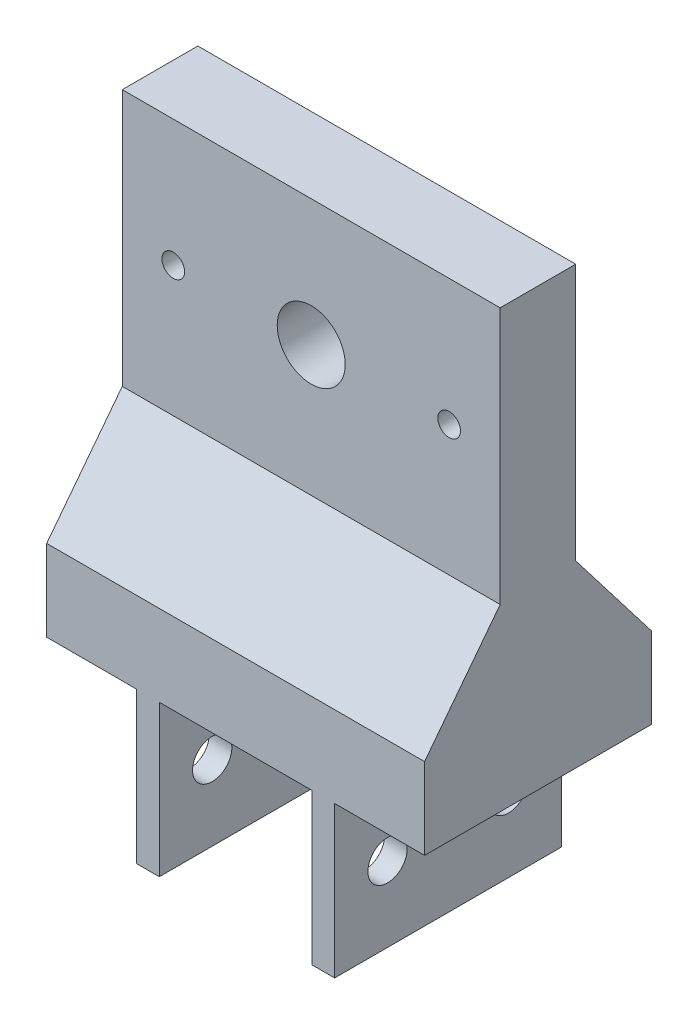
SolidWorks part; units mm, degrees
ref_plane "前视基准面" through (0, 0, 0) normal (0, 0, 1) x (1, 0, 0)
ref_plane "上视基准面" through (0, 0, 0) normal (0, 1, 0) x (1, 0, 0)
ref_plane "右视基准面" through (0, 0, 0) normal (1, 0, 0) x (0, 0, -1)
other "Configuration Table"
sketch "草图1" plane through (0, 0, 0) normal (0, 0, 1) x (1, 0, 0)
  line L0 (0, -39.6057) -> (0, 25.2485) construction
  line L9 (10.1, -25.375) -> (13.1, -25.375)
  line L10 (-25, -5.375) -> (-13.1, -5.375)
  line L11 (-25, -5.375) -> (-25, 5.375)
  line L12 (-25, 5.375) -> (25, 5.375)
  line L13 (25, -5.375) -> (25, 5.375)
  line L14 (-25, -5.375) -> (25, 5.375) construction
  line L15 (-25, 5.375) -> (25, -5.375) construction
  line L16 (-10.1, -5.375) -> (10.1, -5.375)
  line L17 (-13.1, -5.375) -> (-13.1, -25.375)
  line L18 (-13.1, -25.375) -> (-10.1, -25.375)
  line L19 (13.1, -5.375) -> (13.1, -25.375)
  line L21 (-10.1, -25.375) -> (-10.1, -5.375)
  line L22 (-10.1, -5.375) -> (10.1, -5.375)
  line L23 (10.1, -25.375) -> (10.1, -5.375)
  line L24 (-8.4435, -45.2703) -> (10.1, -5.375) construction
  line L25 (-10.1, -5.375) -> (10.5079, -49.7116) construction
  line L26 (-10.1, -5.375) -> (10.1, -5.375)
  line L27 (13.1, -5.375) -> (25, -5.375)
  point P2 (0, 0)
  point P12 (0, -27.1045)
  dimension "D1" = 50
  dimension "D2" = 10.75
  dimension "D3" = 20
  dimension "D4" = 3
  dimension "D5" = 20.2
extrude "凸台-拉伸1" add sketch "草图1" along normal blind 30 contours L19 L27 L13 L12 L11 L10 L17 L18 L21 L16 L23 L9 region at (0, -2.8061, 0)
sketch "草图2" plane through (0, 5.375, 0) normal (0, 1, 0) x (1, 0, 0)
  line L5 (-25, -30) -> (-25, 0) construction
  line L6 (-25, -10) -> (25, -10)
  line L7 (-25, -10) -> (-25, -20)
  line L8 (-25, -20) -> (25, -20)
  line L9 (25, -10) -> (25, -20)
  line L10 (25, -30) -> (25, 0) construction
  line L11 (-25, 0) -> (25, 0) construction
  dimension "D1" = 10
  dimension "D2" = 10
extrude "凸台-拉伸2" add sketch "草图2" along normal blind 50
hole_wizard "孔2" positions "草图8" profile "草图9" legacy end condition through all
sketch "草图8" plane through (-13.1, 0, 0) normal (-1, 0, 0) x (0, 0, 1)
  line L0 (30, -5.375) -> (0, -5.375) construction
  line L1 (0, -5.375) -> (0, -25.375) construction
  line L2 (30, -5.375) -> (30, -25.375) construction
  point P0 (7, -15.375)
  point P2 (23, -15.375)
  point P11 (0, 0)
  point P12 (0, 0)
  point P13 (0, 0)
  point P14 (0, 0)
  dimension "D1" = 10
  dimension "D2" = 10
  dimension "D3" = 7
  dimension "D4" = 7
sketch "草图9" plane through (-13.1, -15.375, 7) normal (0, 1, 0) x (0, 0, 1)
  line L0 (0, 0) -> (0, 38.1)
  line L1 (0, 38.1) -> (2.6, 38.1)
  line L2 (2.6, 38.1) -> (2.6, 0)
  line L3 (2.6, 0) -> (0, 0)
  line L4 (0, 110) -> (0, -10) construction
  dimension "直径" = 5.2
  dimension "深度" = 38.1
hole_wizard "孔3" positions "草图12" profile "草图13" legacy end condition through all
sketch "草图12" plane through (0, 0, 10) normal (0, 0, -1) x (-1, 0, 0)
  line L0 (0, 55.375) -> (0, 5.375) construction
  line L1 (-25, 55.375) -> (25, 55.375) construction
  line L2 (25, 5.375) -> (-25, 5.375) construction
  line L4 (-25, 5.375) -> (25, 5.375) construction
  point P0 (0, 35.625)
  dimension "D1" = 30.25
sketch "草图13" plane through (0, 35.625, 10) normal (1, 0, 0) x (0, 1, 0)
  line L0 (0, 0) -> (0, 20)
  line L1 (0, 20) -> (4.5, 20)
  line L2 (4.5, 20) -> (4.5, 0)
  line L3 (4.5, 0) -> (0, 0)
  line L4 (0, 110) -> (0, -10) construction
  line L5 (-41, 20) -> (-41, -10) construction
  dimension "直径" = 9
  dimension "深度" = 20
sketch "草图17" plane through (0, 0, 10) normal (0, 0, -1) x (-1, 0, 0)
  line L0 (0, 55.375) -> (0, 5.375) construction
  line L1 (-25, 55.375) -> (25, 55.375) construction
  line L2 (25, 5.375) -> (-25, 5.375) construction
  line L3 (-25.3813, 35.625) -> (25.3813, 35.625) construction
  circle A0 centre (18.25, 35.625) radius 2.45
  circle A1 centre (-18.25, 35.625) radius 2.45
  point P10 (0, 35.625)
  dimension "D1" = 4.9
  dimension "D2" = 4.9
  dimension "D3" = 36.5
extrude "凸台-拉伸6" add sketch "草图17" along normal blind 4
hole_wizard "孔5" positions "草图18" profile "草图19" legacy end condition through all
sketch "草图18" plane through (0, 0, 6) normal (0, 0, -1) x (-1, 0, 0)
  point P0 (18.25, 35.625)
  point P3 (-18.25, 35.625)
sketch "草图19" plane through (-18.25, 35.625, 6) normal (1, 0, 0) x (0, 1, 0)
  line L0 (0, 0) -> (0, 24)
  line L1 (0, 24) -> (1.5, 24)
  line L2 (1.5, 24) -> (1.5, 0)
  line L3 (1.5, 0) -> (0, 0)
  line L4 (0, 110) -> (0, -10) construction
  dimension "直径" = 3
  dimension "深度" = 24
sketch "草图20" plane through (-25, 0, 0) normal (-1, 0, 0) x (0, 0, 1)
  line L0 (20, 18.375) -> (30, 5.375)
  line L1 (20, 55.375) -> (20, 5.375) construction
  line L2 (30, -5.375) -> (30, 5.375) construction
  line L3 (30, 5.375) -> (20, 5.375) construction
  line L4 (30, 5.375) -> (20, 5.375)
  line L5 (20, 5.375) -> (20, 18.375)
  line L6 (10, 18.375) -> (0, 5.375)
  line L7 (10, 55.375) -> (10, 5.375) construction
  line L8 (0, 5.375) -> (10, 5.375)
  line L9 (10, 5.375) -> (10, 18.375)
  dimension "D1" = 13
extrude "凸台-拉伸7" add sketch "草图20" against normal up to surface (50 mm away) up to face at (25, 15.1875, 15)
sketch "草图21" plane through (-25, 0, 0) normal (-1, 0, 0) x (0, 0, 1)
  line L0 (10, 55.375) -> (10, 18.375) construction
  line L1 (20, 55.375) -> (10, 55.375)
  line L2 (20, 55.375) -> (20, 52.375)
  line L3 (20, 52.375) -> (10, 52.375)
  line L4 (10, 55.375) -> (10, 52.375)
  dimension "D1" = 3
extrude "切除-拉伸1" cut sketch "草图21" against normal through all
sketch "草图22" plane through (0, 0, 20) normal (0, 0, 1) x (1, 0, 0)
  circle A0 centre (0, 35.625) radius 4.5
  circle A1 centre (0, 35.625) radius 5
  point P4 (0, 0)
  point P5 (0, 0)
  point P6 (0, 0)
  point P7 (0, 0)
  point P8 (0, 0)
  point P9 (0, 0)
  point P10 (0, 0)
  point P11 (0, 0)
  point P12 (0, 0)
  point P13 (0, 0)
  dimension "D1" = 10
